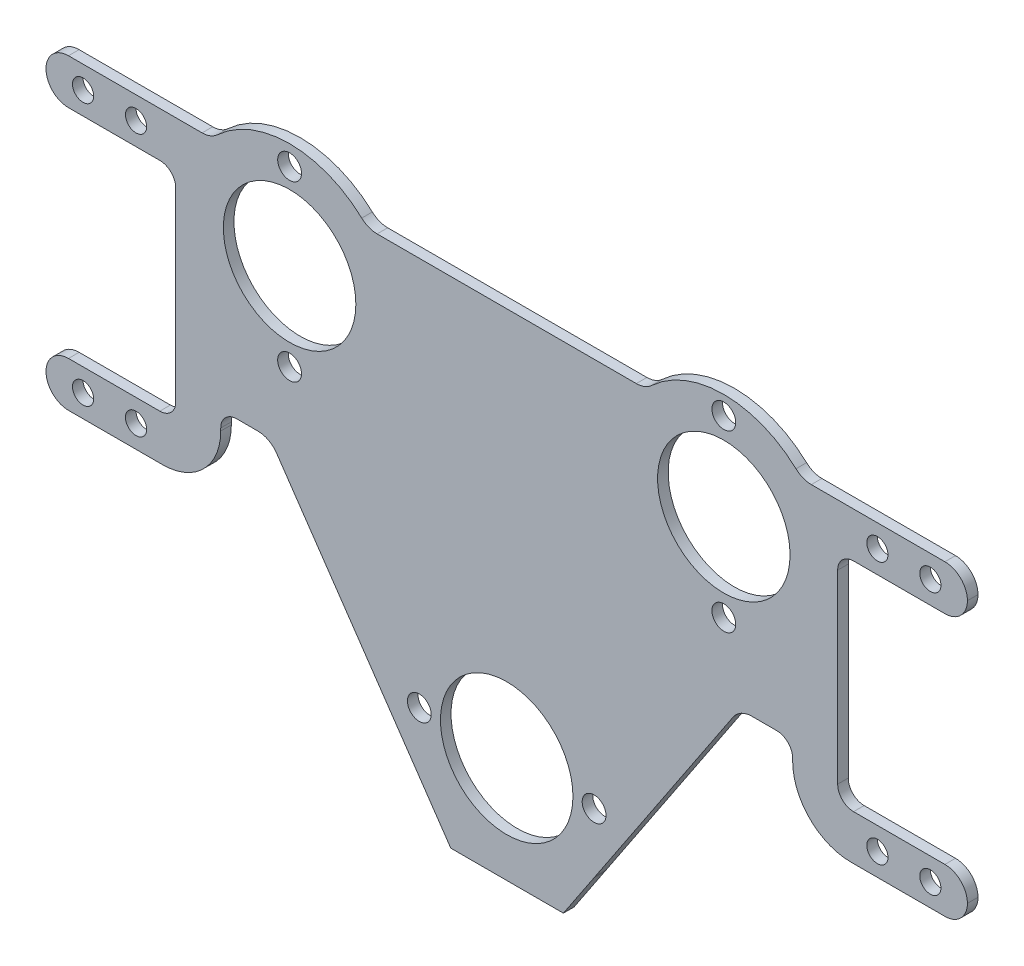
SolidWorks part; units mm, degrees
ref_plane "Front Plane" through (0, 0, 0) normal (0, 0, 1) x (1, 0, 0)
ref_plane "Top Plane" through (0, 0, 0) normal (0, 1, 0) x (1, 0, 0)
ref_plane "Right Plane" through (0, 0, 0) normal (1, 0, 0) x (0, 0, -1)
sketch "Sketch1" plane through (0, 0, 0) normal (0, 0, 1) x (1, 0, 0)
  line L0 (-75, 0) -> (75, 0) construction
  line L5 (-87, 45) -> (87, 45)
  line L6 (-87, 45) -> (-87, -55)
  line L7 (-87, -55) -> (87, -55)
  line L8 (87, 45) -> (87, -55)
  line L9 (-87, 30) -> (87, 30)
  line L10 (-87, -11) -> (87, -11)
  line L11 (-87, -19.5) -> (87, -19.5)
  line L12 (-62.5, 30) -> (-62.5, -11)
  line L13 (-87, 38.5) -> (87, 38.5)
  line L14 (-87, 34.25) -> (87, 34.25) construction
  line L15 (-62.5, 9.5) -> (-135.9991, 9.5) construction
  line L16 (0, 45) -> (0, -55) construction
  line L17 (62.5, 30) -> (62.5, -11)
  line L18 (-54, -19.5) -> (-54, 30)
  line L19 (-54, -5) -> (54, -5)
  line L20 (54, -19.5) -> (54, 30)
  line L21 (-41, 25) -> (0, -35) construction
  line L22 (0, -35) -> (41, 25) construction
  line L23 (41, 25) -> (-41, 25) construction
  line L24 (-10.5568, -55) -> (-44.7235, -5)
  line L25 (10.7046, -55) -> (44.0234, -5)
  circle A1 centre (-80, 34.25) radius 2
  circle A2 centre (-70, 34.25) radius 2
  circle A3 centre (-75, 0) radius 4 construction
  circle A4 centre (-41, 25) radius 12.51
  circle A5 centre (41, 25) radius 12.51
  circle A6 centre (0, -35) radius 12.51
  circle A7 centre (-41, 25) radius 20
  circle A8 centre (41, 25) radius 20
  circle A10 centre (-70, -15.25) radius 2
  circle A11 centre (-80, -15.25) radius 2
  circle A20 centre (80, -15.25) radius 2
  circle A21 centre (70, -15.25) radius 2
  circle A22 centre (70, 34.25) radius 2
  circle A23 centre (80, 34.25) radius 2
  circle A24 centre (0, -35) radius 20
  point P4 (0, -55)
  point P11 (0, 0)
  point P38 (0, -5)
  dimension "D8" = 4
  dimension "D12" = 25.02
  dimension "D16" = 40
  dimension "D1" = 174
  dimension "D2" = 41
  dimension "D3" = 8.5
  dimension "D4" = 8.5
  dimension "D5" = 4.25
  dimension "D6" = 34.25
  dimension "D7" = 10
  dimension "D9" = 80
  dimension "D10" = 8.5
  dimension "D11" = 54
  dimension "D13" = 41
  dimension "D14" = 25
  dimension "D15" = 35
extrude "Boss-Extrude1" add sketch "Sketch1" along normal blind 2 contours A7 L13 L6 L9 A2 A1 | L9 A7 L13 A4 | L13 A7 | A8 L13 A7 L9 | L9 A8 L13 A5 | L13 A8 | A8 L9 L8 L13 A22 A23 | L20 A8 L9 | L9 A8 L20 A5 | L18 A7 L9 A4 | L9 A7 L18 | A7 L9 L12 L10 L18 | A8 L9 A7 L18 L19 L20 | A8 L20 L10 L17 L9 | L20 L11 L8 L10 A21 A20 | L11 L18 L10 L6 A10 A11 | L10 L25 L19 L24 | A24 L11 L25 L10 L24 | A24 L11 L24 | L11 A24 L7 A6 | L11 A24 | A24 L25 L11 | L7 A24 | A24 L24 L7 | A24 L7 L25
fillet "Fillet1" radius 3 6 edges at (62.5, 30, 1) (62.5, -11, 1) (-62.5, -11, 1) (-62.5, 30, 1) (54, -5, 1) (-54, -5, 1)
fillet "Fillet2" radius 4.25 14 edges at (87, 30, 1) (87, 38.5, 1) (87, -11, 1) (87, -19.5, 1) (-87, -19.5, 1) (-87, -11, 1) (-87, 30, 1) (-87, 38.5, 1) (26.2436, 38.5, 1) (55.7564, 38.5, 1) (-55.7564, 38.5, 1) (-26.2436, 38.5, 1) (44.0234, -5, 1) (-44.7235, -5, 1)
fillet "Fillet3" radius 11 2 edges at (-54, -19.5, 1) (54, -19.5, 1)
sketch "Sketch2" plane through (0, 0, 2) normal (0, 0, 1) x (1, 0, 0)
  circle A0 centre (-41, 25) radius 16.5 construction
  circle A1 centre (41, 25) radius 16.5 construction
  circle A2 centre (0, -35) radius 16.5 construction
  circle A5 centre (-41, 41.25) radius 2.25
  circle A6 centre (-41, 8.5) radius 2.25
  circle A7 centre (41, 8.5) radius 2.25
  circle A8 centre (41, 41.5) radius 2.25
  circle A9 centre (-16.5, -35) radius 2.25
  circle A10 centre (16.5, -35) radius 2.25
  dimension "D1" = 4.5
  dimension "D2" = 33
extrude "Cut-Extrude1" cut sketch "Sketch2" against normal up to next
